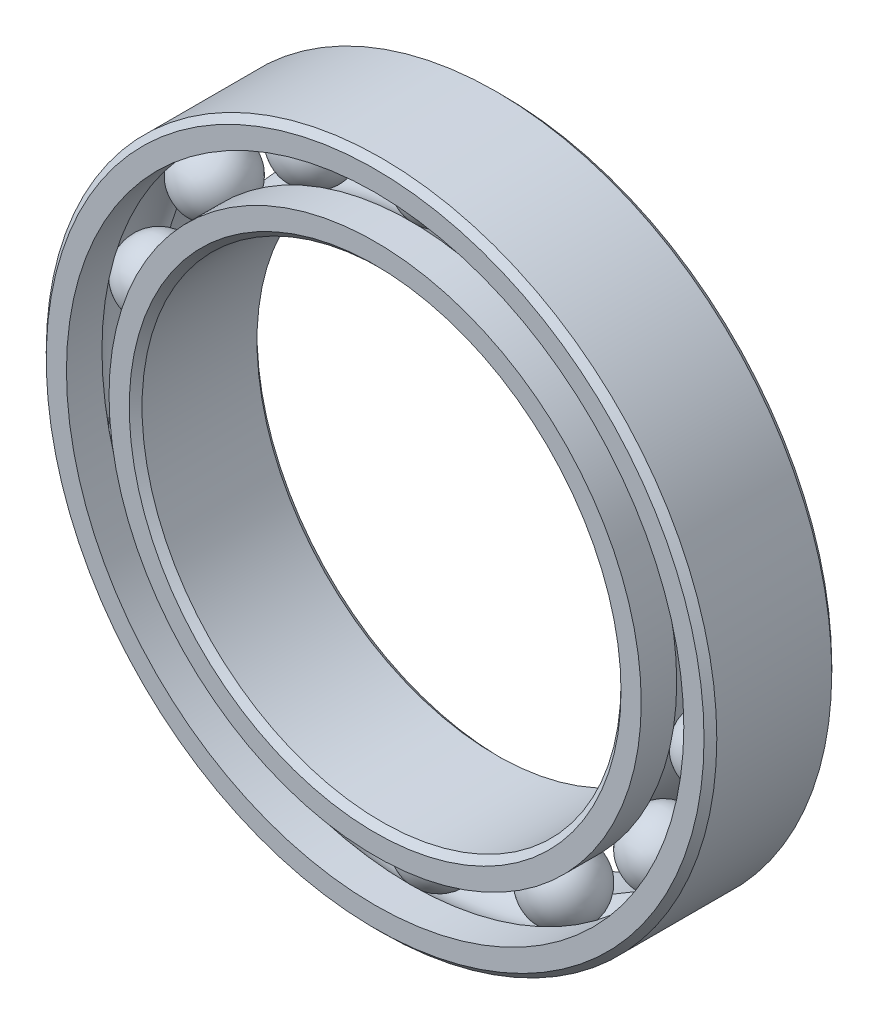
SolidWorks part; units mm, degrees
ref_plane "Front Plane" through (0, 0, 0) normal (0, 0, 1) x (1, 0, 0)
ref_plane "Top Plane" through (0, 0, 0) normal (0, 1, 0) x (1, 0, 0)
ref_plane "Right Plane" through (0, 0, 0) normal (1, 0, 0) x (0, 0, -1)
sketch "Sketch1" plane through (0, 0, 0) normal (0, 0, 1) x (1, 0, 0)
  circle A0 centre (0, 0) radius 10.5
  circle A1 centre (0, 0) radius 7.5
  dimension "OD" = 21
  dimension "ID" = 15
sketch "Sketch5" plane through (0, 0, 0) normal (1, 0, 0) x (0, 0, -1)
  line L0 (-2, 0) -> (2, 0) construction
  line L1 (0, 10.5) -> (0, -10.5) construction
  line L2 (1.8, 10.5) -> (-1.8, 10.5)
  line L3 (-1.8, 10.5) -> (-2, 10.3)
  line L4 (-2, 10.3) -> (-2, 9.6667)
  line L5 (-2, 9.6667) -> (-0.8889, 9.6667)
  line L6 (2, 9.6667) -> (0.8889, 9.6667)
  line L7 (2, 10.3) -> (2, 9.6667)
  line L8 (1.8, 10.5) -> (2, 10.3)
  line L9 (0, 10.5) -> (0, 9) construction
  line L10 (0, 9) -> (0, 7.5) construction
  line L11 (-1.1111, 9) -> (-2, 9) construction
  line L12 (1.3651, 8.3587) -> (1.7461, 8.3587) construction
  line L13 (-1.3651, 8.3587) -> (-1.7461, 8.3587) construction
  line L14 (-1.3651, 8.3587) -> (-1.3651, 9.6413) construction
  line L15 (-1.3651, 9.6413) -> (-1.7461, 9.6413) construction
  line L16 (-1.7461, 8.3587) -> (-1.7461, 9.6413) construction
  line L17 (-1.3651, 8.3587) -> (-1.7461, 9.6413) construction
  line L18 (-1.3651, 9.6413) -> (-1.7461, 8.3587) construction
  line L19 (1.7461, 8.3587) -> (1.7461, 9.6413) construction
  line L20 (1.3651, 9.6413) -> (1.7461, 9.6413) construction
  line L21 (1.3651, 8.3587) -> (1.3651, 9.6413) construction
  line L22 (0, 10.5) -> (0, -10.5) construction
  arc A0 (-0.8889, 9.6667) -> (0.8889, 9.6667) centre (0, 9) cw
  circle A1 centre (0, 9) radius 1.1111 construction
  point P14 (0, 7.5)
  point P15 (-1.5556, 9)
  dimension "Width" = 4
  dimension "D1" = 45
  dimension "D2" = 0.2
  dimension "D3" = 1.7778
  dimension "D4" = 0.6667
  dimension "D5" = 0.381
  dimension "D6" = 0.0254
  dimension "D7" = 4
revolve "Revolve1" add sketch "Sketch5" angle 360 about L0
sketch "Sketch3" plane through (0, 0, 0) normal (1, 0, 0) x (0, 0, -1)
  line L0 (-2, 8.3333) -> (-0.8889, 8.3333)
  line L1 (0, 10.5) -> (0, -10.5) construction
  line L2 (-2, 10.3) -> (-2, 9.6667) construction
  line L3 (-2, 8.3333) -> (-2, 7.7)
  line L4 (-1.8, 10.5) -> (-2, 10.3) construction
  line L5 (-2, 7.7) -> (-1.8, 7.5)
  line L6 (-1.8, 7.5) -> (1.8, 7.5)
  line L7 (1.8, 10.5) -> (1.8, -10.5) construction
  line L8 (1.8, 7.5) -> (2, 7.7)
  line L9 (2, -10.3) -> (2, 10.3) construction
  line L10 (2, 7.7) -> (2, 8.3333)
  line L11 (2, 8.3333) -> (0.8889, 8.3333)
  line L13 (1.8, 10.5) -> (2, 10.3) construction
  arc A0 (0.8889, 9.6667) -> (-0.8889, 9.6667) centre (0, 9) ccw construction
  arc A1 (0.8889, 8.3333) -> (-0.8889, 8.3333) centre (0, 9) cw
revolve "Revolve3" add sketch "Sketch3" angle 360 about L0
sketch "Sketch4" plane through (0, 0, 0) normal (1, 0, 0) x (0, 0, -1)
  line L0 (-1.1111, 9) -> (1.1111, 9)
  arc A2 (-1.1111, 9) -> (1.1111, 9) centre (0, 9) cw
  arc A3 (0.8889, 9.6667) -> (-0.8889, 9.6667) centre (0, 9) ccw construction
revolve "Revolve4" add sketch "Sketch4" angle 360 about L0
pattern_circular "CirPattern1" count 14 every 25.714 of bodies 104
ref_axis "Center Axis 1" through (0, 0, -1.8) along (0, 0, 1)
equation "\"D2@Sketch5\" = \"Width@Sketch5\" * .05"
equation "\"D3@Sketch5\" = \"Width@Sketch5\" / 2.25"
equation "\"D4@Sketch5\"=((\"OD@Sketch1\"-\"ID@Sketch1\")/2)/4.5"
equation "\"D2@CirPattern1\" = 360/\"Balls@CirPattern1\""
